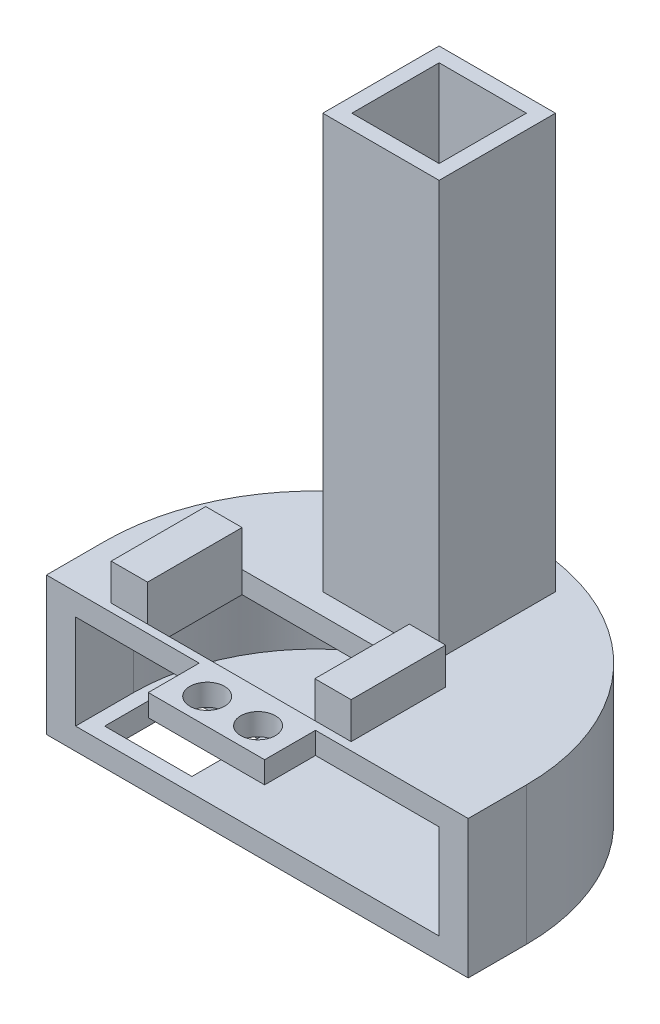
SolidWorks part; units mm, degrees
ref_plane "Front Plane" through (0, 0, 0) normal (0, 0, 1) x (1, 0, 0)
ref_plane "Top Plane" through (0, 0, 0) normal (0, 1, 0) x (1, 0, 0)
ref_plane "Right Plane" through (0, 0, 0) normal (1, 0, 0) x (0, 0, -1)
sketch "Sketch2" plane through (0, 0, 0) normal (0, 1, 0) x (1, 0, 0)
  line L0 (25, 0) -> (-25, 0)
  line L1 (0, 8) -> (0, 33) construction
  line L2 (25, 0) -> (25, 8)
  line L3 (-25, 0) -> (-25, 8)
  line L4 (-29, 0) -> (29, 0)
  line L5 (0, 33) -> (0, 37) construction
  line L6 (6, 19) -> (-6, 19)
  line L7 (6, 19) -> (6, 31)
  line L8 (6, 31) -> (-6, 31)
  line L9 (-6, 19) -> (-6, 31)
  line L10 (6, 19) -> (-6, 31) construction
  line L11 (6, 31) -> (-6, 19) construction
  line L12 (-29, 0) -> (-29, 8)
  line L13 (-23, 14) -> (-11, 14)
  line L14 (-23, 14) -> (-23, 2)
  line L15 (-23, 2) -> (-11, 2)
  line L16 (-11, 14) -> (-11, 2)
  line L17 (23, 2) -> (11, 14) construction
  line L18 (23, 14) -> (11, 2) construction
  line L19 (29, 0) -> (29, 8)
  arc A0 (-25, 8) -> (25, 8) centre (0, 8) cw
  arc A1 (-29, 8) -> (29, 8) centre (0, 8) cw
  point P8 (0, 25)
  point P15 (17, 8)
  point P21 (0, 0)
  dimension "D1" = 58
  dimension "D2" = 25
  dimension "D3" = 4
  dimension "D4" = 17
  dimension "D5" = 12
  dimension "D6" = 12
  dimension "D7" = 17
  dimension "D8" = 12
  dimension "D9" = 12
extrude "Boss-Extrude1" add sketch "Sketch2" along normal blind 16 contours A1 L12 L4 L3 A0 L2 L19 region at (25.688, 0, -4)
extrude "Boss-Extrude2" add sketch "Sketch2<5>" along normal blind 3 contours A0 L3 L0 L2 L6 L9 L8 L7 L13 L16 L15 L14 | L9 L6 L7 L8 region at (2.2382, 0, -13.8228) region at (0, 0, -25)
sketch "Sketch2<5>" plane through (0, 0, 0) normal (0, 1, 0) x (1, 0, 0) same geometry as "Sketch2"
sketch "Sketch3" plane through (0, 16, 0) normal (0, 1, 0) x (1, 0, 0)
  line L0 (-29, 0) -> (-25, 0)
  line L2 (-29, 0) -> (-29, 8)
  line L4 (25, 0) -> (29, 0)
  line L5 (29, 0) -> (29, 8)
  line L6 (-25, 0) -> (25, 0)
  line L7 (-6, 31) -> (6, 31)
  line L8 (-6, 31) -> (-6, 19)
  line L9 (-6, 19) -> (6, 19)
  line L10 (6, 31) -> (6, 19)
  line L11 (8, 17) -> (-8, 17)
  line L12 (8, 17) -> (8, 33)
  line L13 (8, 33) -> (-8, 33)
  line L14 (-8, 17) -> (-8, 33)
  line L15 (8, 17) -> (-8, 33) construction
  line L16 (8, 33) -> (-8, 17) construction
  line L17 (0, 8) -> (9, 8) construction
  line L18 (9, 1.5) -> (9, 14.5)
  line L19 (0, 8) -> (-14, 8) construction
  line L20 (-14, 1.5) -> (-14, 14.5) construction
  line L21 (-16.2, 14.1) -> (6.8, 14.1)
  line L22 (-16.2, 1.1) -> (6.8, 1.1)
  line L23 (-14, 8) -> (-19, 8) construction
  line L24 (9, 8) -> (14, 8) construction
  line L25 (-2.5, 8) -> (-2.5, 4.0917) construction
  line L26 (-21.2, 1.1) -> (-16.2, 1.1)
  line L27 (-21.2, 1.1) -> (-21.2, 14.1)
  line L28 (-21.2, 14.1) -> (-16.2, 14.1)
  line L29 (-16.2, 1.1) -> (-16.2, 14.1)
  line L30 (-19, 1.5) -> (-14, 14.5) construction
  line L31 (-19, 14.5) -> (-14, 1.5) construction
  line L32 (11.8, 1.1) -> (6.8, 1.1)
  line L33 (11.8, 1.1) -> (11.8, 14.1)
  line L34 (11.8, 14.1) -> (6.8, 14.1)
  line L35 (6.8, 1.1) -> (6.8, 14.1)
  line L36 (14, 1.5) -> (9, 14.5) construction
  line L37 (14, 14.5) -> (9, 1.5) construction
  line L38 (0, -7) -> (0, 0) construction
  line L39 (8, -7) -> (-8, -7)
  line L40 (8, -7) -> (8, 0)
  line L41 (8, 0) -> (-8, 0)
  line L42 (-8, -7) -> (-8, 0)
  line L43 (8, -7) -> (-8, 0) construction
  line L44 (8, 0) -> (-8, -7) construction
  arc A1 (-29, 8) -> (29, 8) centre (0, 8) cw
  circle A2 centre (0, 8) radius 2.5
  circle A3 centre (-3.5, -3.4) radius 2.3813
  circle A4 centre (3.5, -3.4) radius 2.3812
  point P5 (-16.5, 8)
  point P24 (0, 25)
  point P31 (9, 8)
  point P34 (-14, 8)
  point P37 (11.5, 8)
  point P52 (0, -3.5)
  arc M3 (29, 8) -> (-29, 8) centre (0, 8) ccw
  line M4 (-29, 8) -> (-29, 0)
  line M5 (-29, 0) -> (-25, 0)
  line M6 (-25, 0) -> (-25, 8)
  arc M7 (-25, 8) -> (25, 8) centre (0, 8) cw
  line M8 (25, 8) -> (25, 0)
  line M9 (25, 0) -> (29, 0)
  line M10 (29, 0) -> (29, 8)
  dimension "D3" = 5
  dimension "D9" = 4.7625
  dimension "D1" = 16
  dimension "D2" = 16
  dimension "D4" = 9
  dimension "D5" = 13
  dimension "D6" = 14
  dimension "D7" = 5
  dimension "D8" = 5
  dimension "D10" = 16
  dimension "D11" = 7
  dimension "D12" = 4.5
  dimension "D13" = 7
extrude "Boss-Extrude3" add sketch "Sketch3" along normal blind 3 contours L14 L13 L12 M7 M8 M9 M10 M3 M4 M5 M6 | L11 L14 L6 L12 M7 M6 M8 | L10 L7 L8 L9 | L14 L13 L12 L11 | L27 L26 L29 L28 | L33 L32 L35 L34 | L40 L39 L42 L41 | A3 | A4 region at (-28.312, 16, -4) region at (2.8654, 16, -14.8311) region at (0, 16, -25)
extrude "Boss-Extrude4" add sketch "Sketch3<4>" along normal blind 60 contours L10 L7 L8 L9 | L12 L13 L14 L11 region at (0, 16, -25)
sketch "Sketch3<4>" plane through (0, 16, 0) normal (0, 1, 0) x (1, 0, 0) same geometry as "Sketch3"
extrude "Boss-Extrude5" add sketch "Sketch3<5>" along normal blind 8 contours L26 L29 L28 L27 | L33 L34 L18 L32 region at (-18.7, 16, -7.6) region at (9.3, 16, -7.6)
sketch "Sketch3<5>" plane through (0, 16, 0) normal (0, 1, 0) x (1, 0, 0) same geometry as "Sketch3"
